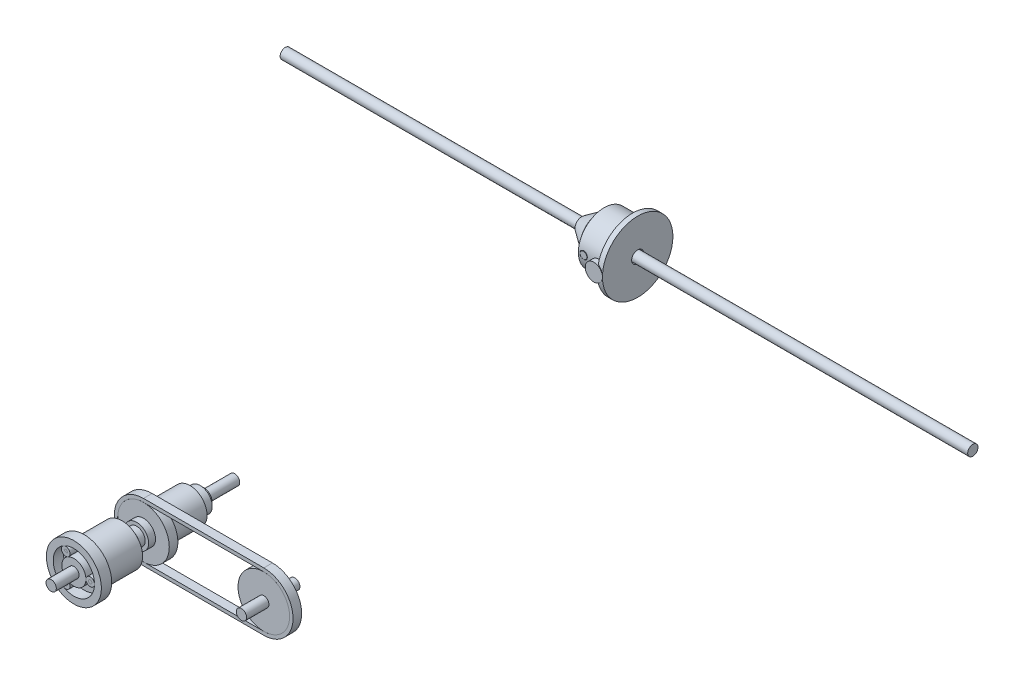
SolidWorks part; units mm, degrees
other "RD Pinion"
other "RD Ring Gear"
other "RD L Gear Right"
other "RD L Gear Left"
other "RD S Gear Outer"
other "RD S Gear Inner"
other "RD S Gear Inner"
other "Main Shaft"
ref_plane "Front Plane" through (0, 0, 0) normal (0, 0, 1) x (1, 0, 0)
ref_plane "Top Plane" through (0, 0, 0) normal (0, 1, 0) x (1, 0, 0)
ref_plane "Right Plane" through (0, 0, 0) normal (1, 0, 0) x (0, 0, -1)
sketch "Top View Layout" plane through (0, 0, 0) normal (0, 1, 0) x (1, 0, 0)
  line L0 (-100, 125) -> (100, 125)
  line L1 (0, 125) -> (0, -125)
  line L2 (-100, -125) -> (100, -125)
  line L3 (0, -15) -> (35, -15) construction
  line L4 (35, -15) -> (35, -125) construction
  line L5 (2.5, 114.75) -> (2.5, 135.25) construction
  line L6 (-2.5, 114.75) -> (2.5, 114.75) construction
  line L7 (-8.75, 127) -> (-2.75, 127) construction
  line L8 (-2.5, 114.75) -> (2.5, 114.75) construction
  line L9 (-2.5, 114.75) -> (-2.5, 116.25) construction
  line L10 (-2.5, 116.25) -> (2.5, 116.25) construction
  line L11 (2.5, 114.75) -> (2.5, 116.25) construction
  line L12 (2.5, 135.25) -> (1, 135.25) construction
  line L13 (2.5, 135.25) -> (2.5, 114.75) construction
  line L14 (2.5, 114.75) -> (1, 114.75) construction
  line L15 (1, 135.25) -> (1, 114.75) construction
  line L16 (-4.25, 128.5) -> (-2.75, 128.5) construction
  line L17 (-4.25, 128.5) -> (-4.25, 121.5) construction
  line L18 (-4.25, 121.5) -> (-2.75, 121.5) construction
  line L19 (-2.75, 128.5) -> (-2.75, 121.5) construction
  line L20 (-4.25, 128.5) -> (-2.75, 121.5) construction
  line L21 (-4.25, 121.5) -> (-2.75, 128.5) construction
  line L22 (-8.75, 128.5) -> (-7.25, 128.5) construction
  line L23 (-8.75, 128.5) -> (-8.75, 121.5) construction
  line L24 (-8.75, 121.5) -> (-7.25, 121.5) construction
  line L25 (-7.25, 128.5) -> (-7.25, 121.5) construction
  line L26 (-8.75, 128.5) -> (-7.25, 121.5) construction
  line L27 (-8.75, 121.5) -> (-7.25, 128.5) construction
  line L28 (-8.75, 123) -> (-2.75, 123) construction
  line L29 (-5.75, 123) -> (-5.75, 120.2863) construction
  line L30 (-5.75, 127) -> (-5.75, 129.2691) construction
  point P8 (0, 114.75)
  point P9 (0, 0)
  point P11 (2.5, 125)
  point P16 (2.5, 125)
  point P19 (0, 114.75)
  point P23 (-3.5, 125)
  point P28 (-8, 125)
  dimension "D1" = 250
  dimension "D2" = 200
  dimension "D3" = 35
  dimension "D4" = 15
  dimension "D5" = 5
  dimension "D6" = 20.5
  dimension "D7" = 1.5
  dimension "D8" = 1.5
  dimension "D9" = 1.5
  dimension "D10" = 7
  dimension "D11" = 3.5
  dimension "D12" = 8
  dimension "D13" = 1.5
  dimension "D14" = 1.5
ref_plane "Left" through (100, 0, 0) normal (-1, 0, 0) x (0, 0, 1)
ref_plane "Right" through (-100, 0, 0) normal (-1, 0, 0) x (0, 0, 1)
sketch "Left Wheels" plane through (100, 0, 0) normal (-1, 0, 0) x (0, 0, 1)
  circle A0 centre (125, 0) radius 25
  circle A1 centre (-125, 0) radius 25
  dimension "D1" = 50
  dimension "D2" = 50
sketch "Right Wheels" plane through (-100, 0, 0) normal (-1, 0, 0) x (0, 0, 1)
  circle A0 centre (-125, 0) radius 25 construction
  circle A1 centre (125, 0) radius 25 construction
  circle A2 centre (-125, 0) radius 25
  circle A3 centre (125, 0) radius 25
ref_plane "Rear Differential Pinion Plane" through (0, 0, -114.75) normal (0, 0, 1) x (1, 0, 0)
sketch "Rear Differential Pinion Profile" plane through (0, 0, -114.75) normal (0, 0, 1) x (1, 0, 0)
  circle A0 centre (0, 0) radius 2.5
ref_plane "Rear Differential Ring Gear Plane" through (2.5, 0, 0) normal (1, 0, 0) x (0, 0, -1)
ref_plane "Rear Axle" through (0, 0, -125) normal (0, 0, 1) x (1, 0, 0)
sketch "Rear Differential Ring Gear Profile" plane through (2.5, 0, 0) normal (1, 0, 0) x (0, 0, -1)
  line L0 (114.75, 0) -> (135.25, 0) construction
  circle A0 centre (125, 0) radius 10.25
extrude "Rear Differential Pinion" add sketch "Rear Differential Pinion Profile" against normal blind 1.5 contours A0
extrude "Rear Differential Ring Gear" add sketch "Rear Differential Ring Gear Profile" against normal blind 1.5 separate body contours A0
ref_plane "RD Inner L Gear Plane" through (-2.75, 0, 0) normal (1, 0, 0) x (0, 0, -1)
ref_plane "RD Outer L Gear Plane" through (-8.75, 0, 0) normal (1, 0, 0) x (0, 0, -1)
sketch "RD Inner L Gear Profile" plane through (-2.75, 0, 0) normal (1, 0, 0) x (0, 0, -1)
  circle A0 centre (125, 0) radius 3.5
sketch "RD Outer L Gear Profile" plane through (-8.75, 0, 0) normal (1, 0, 0) x (0, 0, -1)
  line L0 (128.5, 0) -> (121.5, 0) construction
  circle A0 centre (125, 0) radius 3.5
ref_plane "RD Inner S Gear Plane" through (0, 0, -121.5) normal (0, 0, 1) x (1, 0, 0)
ref_plane "RD Outer S Gear Plane" through (0, 0, -128.5) normal (0, 0, 1) x (1, 0, 0)
sketch "RD Inner S Gear Profile" plane through (0, 0, -121.5) normal (0, 0, 1) x (1, 0, 0)
  line L0 (-8.75, 0) -> (-7.25, 0) construction
  circle A0 centre (-5.75, 0) radius 3
sketch "RD Outer S Gear Profile" plane through (0, 0, -128.5) normal (0, 0, 1) x (1, 0, 0)
  line L0 (-8.75, 0) -> (-7.25, 0) construction
  circle A2 centre (-5.75, 0) radius 3
extrude "RD Outer L Gear Extrude" add sketch "RD Outer L Gear Profile" along normal blind 1.5 separate body contours A0
extrude "RD Inner L Gear Extrude" add sketch "RD Inner L Gear Profile" against normal blind 1.5 separate body contours A0
extrude "RD Outer S Gear Extrude" add sketch "RD Outer S Gear Profile" along normal blind 1.5 separate body contours A2
extrude "RD Inner S Gear Extrude" add sketch "RD Inner S Gear Profile" against normal blind 1.5 separate body contours A0
sketch "RD Ring Gear Case Profile" plane through (1, 0, 0) normal (-1, 0, 0) x (0, 0, 1)
  line L0 (-121.5, 3.2113) -> (-121.5, -3.2113)
  line L1 (-128.5, 3.2113) -> (-128.5, -3.2113)
  line L2 (-121.5, 6.6332) -> (-121.5, 3.2113) construction
  line L3 (-128.5, 6.6332) -> (-128.5, 3.2113) construction
  line L4 (-121.5, -3.2113) -> (-121.5, -6.6332) construction
  line L5 (-128.5, -3.2113) -> (-128.5, -6.6332) construction
  circle A0 centre (-125, 0) radius 7.5
  arc A1 (-121.5, 3.2113) -> (-128.5, 3.2113) centre (-125, 0) ccw
  arc A2 (-121.5, -3.2113) -> (-121.5, 3.2113) centre (-125, 0) ccw construction
  arc A3 (-128.5, 3.2113) -> (-128.5, -3.2113) centre (-125, 0) ccw construction
  arc A4 (-128.5, -3.2113) -> (-121.5, -3.2113) centre (-125, 0) ccw
  point P7 (-121.5, 0)
  dimension "D1" = 15
  dimension "D2" = 9.5
extrude "RD Ring Gear Case " add sketch "RD Ring Gear Case Profile" along normal blind 8.25
sketch "Sketch11" plane through (-7.25, 0, 0) normal (-1, 0, 0) x (0, 0, 1)
  circle A0 centre (-125, 0) radius 5.5
  circle A1 centre (-125, 0) radius 4.75
  arc A2 (-121.5, 3.2113) -> (-128.5, 3.2113) centre (-125, 0) ccw construction
  dimension "D1" = 11
extrude "Boss-Extrude8" add sketch "Sketch11" along normal up to vertex up to point (-8.75, 0, -128.5)
fillet "Fillet1" radius 2 1 edges at (-7.25, 0, -119.5)
sketch "Sketch12" plane through (0, 0, -125) normal (0, 0, 1) x (1, 0, 0)
  line L0 (-8.75, 0) -> (-13.75, 0) construction
  line L1 (-8.75, 0) -> (-7.25, 0) construction
  line L2 (-8.75, 0) -> (-7.25, 0) construction
  line L3 (-100, 0) -> (100, 0) construction
  line L4 (-100, 0) -> (100, 0) construction
  line L5 (-8.75, 5.5) -> (-8.75, -5.5) construction
  line L6 (-13.75, 0) -> (-13.75, 2)
  line L7 (-13.75, 2) -> (-8.75, 5.5)
  line L8 (-13.75, 0) -> (-8.75, 0)
  line L9 (-8.75, 0) -> (-8.75, 5.5)
  point P15 (-13.75, 1)
  dimension "D1" = 5
  dimension "D2" = 2
revolve "Revolve1" add sketch "Sketch12" angle 360 about L0
sketch "Sketch13" plane through (2.5, 0, 0) normal (1, 0, 0) x (0, 0, -1)
  circle A0 centre (125, 0) radius 1.75
  dimension "D1" = 3.5
extrude "Cut-Extrude1" cut sketch "Sketch13" against normal through all
sketch "Sketch14" plane through (0, 0, -121.5) normal (0, 0, 1) x (1, 0, 0)
  circle A0 centre (-5.75, 0) radius 1
  dimension "D1" = 2
extrude "Boss-Extrude9" add sketch "Sketch14" along normal blind 4
sketch "Sketch15" plane through (0, 0, -121.5) normal (0, 0, 1) x (1, 0, 0)
  circle A0 centre (-5.75, 0) radius 1.1
  dimension "D1" = 2.2
extrude "Cut-Extrude2" cut sketch "Sketch15" against normal through all both and the other way through all
extrude "Boss-Extrude10" add sketch "Sketch14<2>" against normal blind 4 from surface starting at face at (-2.75, 0, -128.5)
sketch "Sketch14<2>" plane through (0, 0, -121.5) normal (0, 0, 1) x (1, 0, 0) same geometry as "Sketch14"
sketch "Sketch16" plane through (-8.75, 0, 0) normal (-1, 0, 0) x (0, 0, 1)
  circle A0 centre (-125, 0) radius 1.5
  dimension "D1" = 3
extrude "Boss-Extrude11" add sketch "Sketch16" along normal up to vertex (91.25 mm away) up to point (-100, 0, -125)
sketch "Sketch17" plane through (-2.75, 0, 0) normal (1, 0, 0) x (0, 0, -1)
  circle A0 centre (125, 0) radius 1.5 construction
  circle A1 centre (125, 0) radius 1.5
extrude "Boss-Extrude12" add sketch "Sketch17" along normal up to vertex (102.75 mm away) up to point (100, 0, -125)
sketch "Transfer Case Layout" plane through (0, 0, 0) normal (0, 1, 0) x (1, 0, 0)
  line L0 (0, 125) -> (0, -125) construction
  line L1 (-7.5, -13.75) -> (7.5, -13.75)
  line L2 (-7.5, -13.75) -> (-7.5, -16.25)
  line L3 (-7.5, -16.25) -> (7.5, -16.25)
  line L4 (7.5, -13.75) -> (7.5, -16.25)
  line L5 (-7.5, -13.75) -> (7.5, -16.25) construction
  line L6 (-7.5, -16.25) -> (7.5, -13.75) construction
  line L7 (27.5, -13.75) -> (42.5, -13.75)
  line L8 (27.5, -13.75) -> (27.5, -16.25)
  line L9 (27.5, -16.25) -> (42.5, -16.25)
  line L10 (42.5, -13.75) -> (42.5, -16.25)
  line L11 (27.5, -13.75) -> (42.5, -16.25) construction
  line L12 (27.5, -16.25) -> (42.5, -13.75) construction
  line L13 (2.5, -17.25) -> (-2.5, -17.25)
  line L14 (2.5, -17.25) -> (2.5, -16.25)
  line L15 (2.5, -16.25) -> (-2.5, -16.25)
  line L16 (-2.5, -17.25) -> (-2.5, -16.25)
  line L17 (2.5, -17.25) -> (-2.5, -16.25) construction
  line L18 (2.5, -16.25) -> (-2.5, -17.25) construction
  line L19 (-2, -4.75) -> (-2, -10.75)
  line L20 (3.5, -18.25) -> (-3.5, -18.25)
  line L21 (3.5, -18.25) -> (3.5, -16.25)
  line L22 (3.5, -16.25) -> (-3.5, -16.25)
  line L23 (-3.5, -18.25) -> (-3.5, -16.25)
  line L24 (3.5, -18.25) -> (-3.5, -16.25) construction
  line L25 (3.5, -16.25) -> (-3.5, -18.25) construction
  line L26 (2.5, -20) -> (-2.5, -20)
  line L27 (2.5, -20) -> (2.5, -17.5)
  line L28 (2.5, -17.5) -> (-2.5, -17.5)
  line L29 (-2.5, -20) -> (-2.5, -17.5)
  line L30 (2.5, -20) -> (-2.5, -17.5) construction
  line L31 (2.5, -17.5) -> (-2.5, -20) construction
  line L32 (-3.5, -9.25) -> (3.5, -9.25)
  line L33 (-3.5, -9.25) -> (-3.5, -10.75)
  line L34 (-3.5, -10.75) -> (3.5, -10.75)
  line L35 (3.5, -9.25) -> (3.5, -10.75)
  line L36 (-3.5, -9.25) -> (3.5, -10.75) construction
  line L37 (-3.5, -10.75) -> (3.5, -9.25) construction
  line L38 (-3.5, -4.75) -> (3.5, -4.75)
  line L39 (-3.5, -4.75) -> (-3.5, -6.25)
  line L40 (-3.5, -6.25) -> (3.5, -6.25)
  line L41 (3.5, -4.75) -> (3.5, -6.25)
  line L42 (-3.5, -4.75) -> (3.5, -6.25) construction
  line L43 (-3.5, -6.25) -> (3.5, -4.75) construction
  line L44 (2, -4.75) -> (2, -10.75)
  line L45 (0, -6.25) -> (0, -9.25) construction
  line L46 (-5, -2.75) -> (5, -2.75) construction
  line L47 (-5, -2.75) -> (-5, -12.75) construction
  line L48 (-5, -12.75) -> (5, -12.75) construction
  line L49 (5, -2.75) -> (5, -12.75) construction
  line L50 (-5, -2.75) -> (5, -12.75) construction
  line L51 (-5, -12.75) -> (5, -2.75) construction
  line L52 (-6, -22.5) -> (-6, -24)
  line L53 (-2.5, -1.75) -> (2.5, -1.75)
  line L54 (-2.5, -1.75) -> (-2.5, -2.75)
  line L55 (-2.5, -2.75) -> (2.5, -2.75)
  line L56 (2.5, -1.75) -> (2.5, -2.75)
  line L57 (-2.5, -1.75) -> (2.5, -2.75) construction
  line L58 (-2.5, -2.75) -> (2.5, -1.75) construction
  line L59 (-2.5, 1.25) -> (2.5, 1.25)
  line L60 (-2.5, 1.25) -> (-2.5, -0.75)
  line L61 (-2.5, -0.75) -> (2.5, -0.75)
  line L62 (2.5, 1.25) -> (2.5, -0.75)
  line L63 (-2.5, 1.25) -> (2.5, -0.75) construction
  line L64 (-2.5, -0.75) -> (2.5, 1.25) construction
  line L65 (3.5, 0.25) -> (-3.5, 0.25)
  line L66 (3.5, 0.25) -> (3.5, -2.25)
  line L67 (3.5, -2.25) -> (-3.5, -2.25)
  line L68 (-3.5, 0.25) -> (-3.5, -2.25)
  line L69 (3.5, 0.25) -> (-3.5, -2.25) construction
  line L70 (3.5, -2.25) -> (-3.5, 0.25) construction
  line L71 (-2.5, -22.5) -> (2.5, -22.5)
  line L72 (-2.5, -22.5) -> (-2.5, -27.5)
  line L73 (-2.5, -27.5) -> (2.5, -27.5)
  line L74 (2.5, -22.5) -> (2.5, -27.5)
  line L75 (-2.5, -22.5) -> (2.5, -27.5) construction
  line L76 (-2.5, -27.5) -> (2.5, -22.5) construction
  line L77 (-6, -24) -> (6, -24)
  line L78 (6, -24) -> (6, -22.5)
  line L79 (6, -22.5) -> (-6, -22.5)
  line L80 (-4.5, -22.5) -> (-4.5, -24)
  line L81 (4.5, -22.5) -> (4.5, -24)
  line L82 (-6, -24) -> (-6, -33.5) construction
  line L83 (2.5, -29.5) -> (-2.5, -29.5)
  line L84 (2.5, -29.5) -> (2.5, -28)
  line L85 (2.5, -28) -> (-2.5, -28)
  line L86 (-2.5, -29.5) -> (-2.5, -28)
  line L87 (2.5, -29.5) -> (-2.5, -28) construction
  line L88 (2.5, -28) -> (-2.5, -29.5) construction
  line L89 (-4.5, -26.5) -> (4.5, -26.5)
  line L90 (-4.5, -26.5) -> (-4.5, -29.5)
  line L91 (-4.5, -29.5) -> (4.5, -29.5)
  line L92 (4.5, -26.5) -> (4.5, -29.5)
  line L93 (-4.5, -26.5) -> (4.5, -29.5) construction
  line L94 (-4.5, -29.5) -> (4.5, -26.5) construction
  line L95 (6, -24) -> (6, -33.5) construction
  line L96 (-3.5, -33.5) -> (-3.5, -36.5)
  line L97 (6, -36.5) -> (-6, -36.5)
  line L98 (6, -36.5) -> (6, -33.5)
  line L99 (6, -33.5) -> (-6, -33.5)
  line L100 (-6, -36.5) -> (-6, -33.5)
  line L101 (6, -36.5) -> (-6, -33.5) construction
  line L102 (6, -33.5) -> (-6, -36.5) construction
  line L103 (3.5, -33.5) -> (3.5, -36.5)
  line L104 (0, -28) -> (0, -43.1129)
  line L109 (8, -36.5) -> (-8, -36.5)
  line L110 (8, -36.5) -> (8, -33.5)
  line L111 (8, -33.5) -> (-8, -33.5)
  line L112 (-8, -36.5) -> (-8, -33.5)
  line L113 (8, -36.5) -> (-8, -33.5) construction
  line L114 (8, -33.5) -> (-8, -36.5) construction
  line L115 (0, -27.5) -> (0, -9.25)
  line L116 (0, -6.25) -> (0, -1.75)
  line L117 (0, -0.75) -> (0, 11.0375)
  line L118 (35, -22.7597) -> (35, -7.2403)
  point P0 (0, -15)
  point P6 (35, -15)
  point P12 (0, -16.75)
  point P19 (0, -17.25)
  point P24 (0, -18.75)
  point P29 (0, -10)
  point P34 (0, -5.5)
  point P43 (0, -7.75)
  point P50 (0, -2.25)
  point P55 (0, 0.25)
  point P60 (0, -1)
  point P65 (0, -25)
  point P72 (0, -22.5)
  point P79 (0, -28.75)
  point P84 (0, -28)
  point P92 (0, -35)
  point P98 (0, -35)
  point P99 (0, -35)
  point P113 (35, -15)
  dimension "D1" = 2.5
  dimension "D2" = 2.5
  dimension "D3" = 15
  dimension "D4" = 15
  dimension "D5" = 1
  dimension "D6" = 5
  dimension "D7" = 7
  dimension "D8" = 2
  dimension "D9" = 0.25
  dimension "D10" = 2.5
  dimension "D11" = 7
  dimension "D12" = 5
  dimension "D13" = 1.5
  dimension "D14" = 1.5
  dimension "D15" = 1.5
  dimension "D16" = 1.5
  dimension "D17" = 6
  dimension "D18" = 2
  dimension "D19" = 1.5
  dimension "D20" = 5
  dimension "D21" = 1
  dimension "D22" = 2
  dimension "D23" = 1
  dimension "D24" = 7
  dimension "D25" = 2.5
  dimension "D26" = 0.5
  dimension "D27" = 5
  dimension "D28" = 5
  dimension "D29" = 10
  dimension "D30" = 1.5
  dimension "D31" = 12
  dimension "D32" = 1.5
  dimension "D33" = 1.5
  dimension "D34" = 1.5
  dimension "D35" = 0.5
  dimension "D36" = 3
  dimension "D37" = 3
  dimension "D38" = 20
  dimension "D39" = 2.5
  dimension "D40" = 2.5
  dimension "D41" = 7
  dimension "D42" = 2
  dimension "D43" = 16
ref_plane "FWD Sprocket Plane" through (0, 0, 15) normal (0, 0, 1) x (1, 0, 0)
sketch "Sketch19" plane through (0, 0, 15) normal (0, 0, 1) x (1, 0, 0)
  circle A0 centre (35, 0) radius 7.5
  circle A1 centre (0, 0) radius 7.5
  point P6 (7.5, 0)
  point P9 (27.5, 0)
extrude "FWD Sprockets" add sketch "Sketch19" along normal up to vertex (1.25 mm away) and the other way up to vertex (1.25 mm away) separate body up to point (-7.5, 0, 16.25) other way up to point (-7.5, 0, 13.75)
sketch "Sketch20" plane through (0, 0, 15) normal (0, 0, 1) x (1, 0, 0)
  line L0 (0, 8.5) -> (35, 8.5)
  line L1 (0, -8.5) -> (35, -8.5)
  line L2 (0, 7.5) -> (35, 7.5)
  line L3 (0, -7.5) -> (35, -7.5)
  circle A0 centre (0, 0) radius 7.5 construction
  arc A1 (0, 7.5) -> (0, -7.5) centre (0, 0) ccw
  circle A2 centre (35, 0) radius 7.5 construction
  arc A3 (35, -7.5) -> (35, 7.5) centre (35, 0) ccw
  arc A4 (0, 8.5) -> (0, -8.5) centre (0, 0) ccw
  arc A5 (35, -8.5) -> (35, 8.5) centre (35, 0) ccw
  arc A6 (4, -7.5) -> (4, 7.5) centre (0, 0) ccw construction
  arc A7 (0, -7.5) -> (0, 7.5) centre (0, 0) ccw construction
  arc A8 (35, 7.5) -> (35, -7.5) centre (35, 0) ccw construction
  arc A9 (31, 7.5) -> (31, -7.5) centre (35, 0) ccw construction
  arc A10 (4, 7.5) -> (0, 8.5) centre (0, 0) ccw construction
  arc A11 (35, 8.5) -> (31, 7.5) centre (35, 0) ccw construction
  arc A12 (31, -7.5) -> (35, -8.5) centre (35, 0) ccw construction
  arc A13 (0, -8.5) -> (4, -7.5) centre (0, 0) ccw construction
  dimension "D1" = 1
  dimension "D2" = 1
extrude "FWD Sprocket Chain" add sketch "Sketch20" along normal up to surface and the other way up to surface separate body up to face at (7.5, 0, 16.25) other way up to face at (7.5, 0, 13.75)
sketch "Sketch21" plane through (0, 0, 16.25) normal (0, 0, 1) x (1, 0, 0)
  circle A0 centre (0, 0) radius 2.5
  point P3 (2.5, 0)
extrude "FWD Sprocket Dog Gear" add sketch "Sketch21" along normal up to vertex (1 mm away) up to point (-2.5, 0, 17.25)
ref_plane "Mode Sleeve Gear Plane" through (0, 0, 18.25) normal (0, 0, 1) x (1, 0, 0)
sketch "Sketch22" plane through (0, 0, 18.25) normal (0, 0, 1) x (1, 0, 0)
  circle A0 centre (0, 0) radius 3.5
  circle A1 centre (0, 0) radius 2.5 construction
  circle A2 centre (0, 0) radius 2.5
extrude "Mode Sleeve Gear" add sketch "Sketch22" against normal up to vertex (2 mm away) separate body up to point (3.5, 0, 16.25)
sketch "Sketch23" plane through (0, 0, 18.25) normal (0, 0, 1) x (1, 0, 0)
  circle A0 centre (0, 0) radius 2.5 construction
  circle A1 centre (0, 0) radius 2.5
extrude "Mode Sleeve Main Shaft Gear" add sketch "Sketch23" along normal up to vertex (1.75 mm away) separate body up to point (2.5, 0, 20)
ref_plane "Range Sleeve Rear Plane" through (0, 0, 22.5) normal (0, 0, 1) x (1, 0, 0)
sketch "Sketch24" plane through (0, 0, 22.5) normal (0, 0, 1) x (1, 0, 0)
  circle A0 centre (0, 0) radius 2.5
extrude "Main Shaft Range Sleeve Gear" add sketch "Sketch24" along normal up to vertex (5 mm away) separate body up to point (-2.5, 0, 27.5)
sketch "Sketch25" plane through (0, 0, 22.5) normal (0, 0, 1) x (1, 0, 0)
  circle A0 centre (0, 0) radius 6
  circle A3 centre (0, 0) radius 4.5
extrude "Carrier Range Sleeve Gear" add sketch "Sketch25" along normal up to vertex (1.5 mm away) separate body up to point (6, 0, 24)
ref_plane "Range Sleeve Input Shaft Side" through (0, 0, 29.5) normal (0, 0, 1) x (1, 0, 0)
sketch "Sketch27" plane through (0, 0, 29.5) normal (0, 0, 1) x (1, 0, 0)
  circle A0 centre (0, 0) radius 2.5
extrude "Input Range Sleeve Gear" add sketch "Sketch27" against normal up to vertex (1.5 mm away) separate body up to point (2.5, 0, 28)
sketch "Sketch28" plane through (0, 0, 29.5) normal (0, 0, 1) x (1, 0, 0)
  circle A0 centre (0, 0) radius 4.5
  circle A1 centre (0, 0) radius 2.5 construction
  circle A2 centre (0, 0) radius 2.5
extrude "Range Sleeve Sleeve Gear" add sketch "Sketch28" against normal up to vertex (3 mm away) separate body up to point (4.5, 0, 26.5)
ref_plane "Planetary Input Side Plane" through (0, 0, 36.5) normal (0, 0, 1) x (1, 0, 0)
sketch "Sketch29" plane through (0, 0, 36.5) normal (0, 0, 1) x (1, 0, 0)
  circle A0 centre (0, 0) radius 3.5
extrude "Planetary Sun Gear" add sketch "Sketch29" against normal up to vertex (3 mm away) separate body up to point (3.5, 0, 33.5)
sketch "Sketch30" plane through (0, 0, 36.5) normal (0, 0, 1) x (1, 0, 0)
  line L0 (6, 0) -> (-6, 0) construction
  circle A0 centre (4.75, 0) radius 1.25
extrude "Planetary Planet Gear" add sketch "Sketch30" against normal up to vertex (3 mm away) separate body up to point (6, 0, 33.5)
pattern_circular "Planetary Planet Gear x 3" count 3 over 360 about axis through (0, 0, 28) along (0, 0, 1) reverse direction yes of bodies 132
sketch "Sketch31" plane through (0, 0, 36.5) normal (0, 0, 1) x (1, 0, 0)
  circle A0 centre (0, 0) radius 6
  circle A1 centre (0, 0) radius 8
extrude "Planetary Ring Gear" add sketch "Sketch31" against normal up to vertex (3 mm away) separate body up to point (8, 0, 33.5)
ref_plane "Planetary Rear Side Plane" through (0, 0, 33.5) normal (0, 0, 1) x (1, 0, 0)
sketch "Sketch32" plane through (0, 0, 33.5) normal (0, 0, 1) x (1, 0, 0)
  line L0 (3.5, 0) -> (6, 0) construction
  line L1 (0, 0) -> (4.75, 0) construction
  line L2 (0, 0) -> (-2.375, -4.1136) construction
  circle A0 centre (0, 0) radius 6
  circle A1 centre (4.75, 0) radius 0.5
  circle A2 centre (-2.375, -4.1136) radius 0.5
  circle A3 centre (-2.375, 4.1136) radius 0.5
  point P4 (4.75, 0)
  dimension "D1" = 1
  dimension "D3" = 120
  dimension "D4" = 4.75
  dimension "D2" = 3
extrude "Carrier" add sketch "Sketch32" against normal blind 1 separate body contours A3 | A0 A3 A2 A1 | A1 | A2 region at (0, 0, 33.5) region at (4.75, 0, 33.5) region at (-2.375, -4.1136, 33.5) region at (-2.375, 4.1136, 33.5)
extrude "Carrier Shafts" add sketch "Sketch32<3>" along normal up to vertex (3 mm away) contours A1 | A2 | A3 region at (4.75, 0, 33.5) region at (-2.375, -4.1136, 33.5) up to point (-3.5, 0, 36.5)
sketch "Sketch32<3>" plane through (0, 0, 33.5) normal (0, 0, 1) x (1, 0, 0) same geometry as "Sketch32"
sketch "Sketch33" plane through (0, 0, 33.5) normal (0, 0, 1) x (1, 0, 0)
  circle A0 centre (0, 0) radius 6 construction
  circle A1 centre (0, 0) radius 6
  circle A2 centre (0, 0) radius 5.5
  dimension "D1" = 0.5
extrude "Carrier Range Sleeve Gear Connect" add sketch "Sketch33" against normal up to surface (9.5 mm away) up to face at (6, 0, 24)
ref_plane "Center Diff Main Shaft Sidegear Plane" through (0, 0, 10.75) normal (0, 0, 1) x (1, 0, 0)
sketch "Sketch34" plane through (0, 0, 10.75) normal (0, 0, 1) x (1, 0, 0)
  circle A0 centre (0, 0) radius 3.5
extrude "Center Diff Main Shaft Side Gear" add sketch "Sketch34" against normal up to vertex (1.5 mm away) separate body up to point (3.5, 0, 9.25)
ref_plane "Center Diff Rear Shaft Sidegear Plane" through (0, 0, 4.75) normal (0, 0, 1) x (1, 0, 0)
ref_plane "Center Diff Mid Plane" through (0, 0, 7.75) normal (0, 0, 1) x (1, 0, 0)
mirror "Center Diff Rear Shaft Side Gear" about plane through (0, 0, 7.75) normal (0, 0, 1) of bodies 139
ref_plane "Center Diff Right Pinion Inner Plane" through (-2, 0, 0) normal (-1, 0, 0) x (0, 0, 1)
sketch "Sketch35" plane through (-2, 0, 0) normal (-1, 0, 0) x (0, 0, 1)
  line L0 (4.75, 0) -> (10.75, 0) construction
  circle A0 centre (7.75, 0) radius 3
extrude "Center Diff Right Pinion" add sketch "Sketch35" along normal up to vertex (1.5 mm away) separate body up to point (-3.5, 0, 10.75)
ref_plane "Center Diff Left Side Pinion Inner Plane" through (2, 0, 0) normal (-1, 0, 0) x (0, 0, 1)
sketch "Sketch36" plane through (2, 0, 0) normal (-1, 0, 0) x (0, 0, 1)
  line L0 (4.75, 0) -> (10.75, 0) construction
  circle A0 centre (7.75, 0) radius 3
extrude "Center Diff Left Pinion" add sketch "Sketch36" against normal up to vertex (1.5 mm away) separate body up to point (3.5, 0, 4.75)
ref_plane "Center Diff Rear Shaft Side Plane" through (0, 0, 2.75) normal (0, 0, 1) x (1, 0, 0)
sketch "Sketch37" plane through (0, 0, 2.75) normal (0, 0, 1) x (1, 0, 0)
  circle A0 centre (0, 0) radius 5
extrude "Center Diff Rear Axle Side Plate" add sketch "Sketch37" along normal up to vertex (2 mm away) separate body up to point (3.5, 0, 4.75)
mirror "Center Diff Main Shaft Side Plate" about plane through (0, 0, 7.75) normal (0, 0, 1) of bodies 143
sketch "Sketch38" plane through (0, 0, 2.75) normal (0, 0, 1) x (1, 0, 0)
  line L0 (3.5, -2.8284) -> (3.5, 2.8284)
  line L1 (-3.4263, -2.9173) -> (-3.5, -2.8284)
  line L2 (-3.5, -2.8284) -> (-3.5, 2.8284)
  circle A0 centre (0, 0) radius 5 construction
  circle A1 centre (0, 0) radius 5
  arc A2 (3.5, 2.8284) -> (-3.5, 2.8284) centre (0, 0) ccw
  arc A3 (3.5, -2.8284) -> (3.5, 2.8284) centre (0, 0) ccw construction
  arc A4 (-3.5, 2.8284) -> (-3.5, -2.8284) centre (0, 0) ccw construction
  arc A5 (-3.5, -2.8284) -> (3.5, -2.8284) centre (0, 0) ccw
  dimension "D1" = 0.5
extrude "Center Diff Case" add sketch "Sketch38" along normal up to surface (8 mm away) contours A1 A5 L2 A2 L0 region at (-4.8586, 0, 2.75) up to face at (5, 0, 10.75)
sketch "Sketch39" plane through (0, 0, 2.75) normal (0, 0, 1) x (1, 0, 0)
  circle A0 centre (0, 0) radius 2.5
extrude "Center Diff Lock Gear" add sketch "Sketch39" against normal up to vertex (1 mm away) up to point (2.5, 0, 1.75)
ref_plane "Lock Sleeve Plane" through (0, 0, -0.25) normal (0, 0, 1) x (1, 0, 0)
sketch "Sketch41" plane through (0, 0, -0.25) normal (0, 0, 1) x (1, 0, 0)
  circle A0 centre (0, 0) radius 3.5
  circle A1 centre (0, 0) radius 2.5 construction
  circle A2 centre (0, 0) radius 2.5
extrude "Lock Sleeve" add sketch "Sketch41" along normal up to vertex (2.5 mm away) separate body up to point (-3.5, 0, 2.25)
sketch "Sketch42" plane through (0, 0, -0.25) normal (0, 0, 1) x (1, 0, 0)
  circle A0 centre (0, 0) radius 2.5 construction
  circle A1 centre (0, 0) radius 2.5
extrude "Lock Sleeve Rear Shaft Gear" add sketch "Sketch42" along normal up to vertex (1 mm away) and the other way up to vertex (1 mm away) separate body up to point (2.5, 0, 0.75) other way up to point (2.5, 0, -1.25)
sketch "Sketch43" plane through (-2, 0, 0) normal (-1, 0, 0) x (0, 0, 1)
  line L0 (4.75, 0) -> (10.75, 0) construction
  circle A0 centre (7.75, 0) radius 0.5
  dimension "D1" = 1
extrude "Center Diff Pinion Rotation Point Cut" cut sketch "Sketch43" against normal through all both and the other way through all
sketch "Sketch45" plane through (0, 0, 2.75) normal (0, 0, 1) x (1, 0, 0)
  circle A0 centre (0, 0) radius 0.5
  dimension "D1" = 1
extrude "Center Diff Side Gear Rotation Point" cut sketch "Sketch45" against normal through all both and the other way through all
sketch "Sketch46" plane through (0, 0, -0.25) normal (0, 0, 1) x (1, 0, 0)
  circle A0 centre (0, 0) radius 1.5
  dimension "D1" = 3
extrude "Rear Shaft" add sketch "Sketch46" along normal up to vertex (1 mm away) and the other way blind 10 up to point (0, 0, 0.75)
sketch "Sketch47" plane through (0, 0, 2.75) normal (0, 0, 1) x (1, 0, 0)
  circle A0 centre (0, 0) radius 0.5
  dimension "D1" = 1
extrude "Center Diff Rear Shaft Side Axle" add sketch "Sketch47" along normal up to vertex (3.5 mm away) and the other way up to vertex (1 mm away) up to point (0, 0, 6.25) other way up to point (0, 0, 1.75)
sketch "Sketch48" plane through (-2, 0, 0) normal (-1, 0, 0) x (0, 0, 1)
  circle A0 centre (7.75, 0) radius 0.5 construction
  circle A1 centre (7.75, 0) radius 0.5
extrude "Center Diff Right Side Pinion Axle" add sketch "Sketch48" along normal up to vertex (3 mm away) up to point (-5, 0, 12.75)
sketch "Sketch49" plane through (2, 0, 0) normal (-1, 0, 0) x (0, 0, 1)
  circle A0 centre (7.75, 0) radius 0.5 construction
  circle A1 centre (7.75, 0) radius 0.5
extrude "Center Diff Left Side Pinion Axle" add sketch "Sketch49" against normal up to vertex (3 mm away) up to point (5, 0, 2.75)
sketch "Sketch50" plane through (0, 0, 18.25) normal (0, 0, 1) x (1, 0, 0)
  circle A0 centre (0, 0) radius 0.5
  dimension "D1" = 1
extrude "Main Shaft Sprocket Rotation Point Cut" cut sketch "Sketch50" against normal through all both and the other way through all
extrude "Main Shaft Extrude" add sketch "Sketch50<2>" against normal up to vertex (9 mm away) and the other way up to vertex (9.25 mm away) up to point (0, 0, 9.25) other way up to point (0, 0, 27.5)
sketch "Sketch50<2>" plane through (0, 0, 18.25) normal (0, 0, 1) x (1, 0, 0) same geometry as "Sketch50"
sketch "Sketch52" plane through (0, 0, 36.5) normal (0, 0, 1) x (1, 0, 0)
  circle A0 centre (0, 0) radius 1.5
  dimension "D1" = 3
extrude "Input Shaft Carrier Cut" cut sketch "Sketch52" against normal through all both and the other way through all
extrude "Input Shaft" add sketch "Sketch52<2>" along normal up to vertex (6.6129 mm away) and the other way up to vertex (8.5 mm away) up to point (0, 0, 43.1129) other way up to point (0, 0, 28)
sketch "Sketch52<2>" plane through (0, 0, 36.5) normal (0, 0, 1) x (1, 0, 0) same geometry as "Sketch52"
sketch "Sketch54" plane through (0, 0, 15) normal (0, 0, 1) x (1, 0, 0)
  circle A0 centre (35, 0) radius 1.5
  dimension "D1" = 3
extrude "FW Shaft" add sketch "Sketch54" along normal up to vertex (7.7597 mm away) and the other way up to vertex (7.7597 mm away) up to point (35, 0, 22.7597) other way up to point (35, 0, 7.2403)
